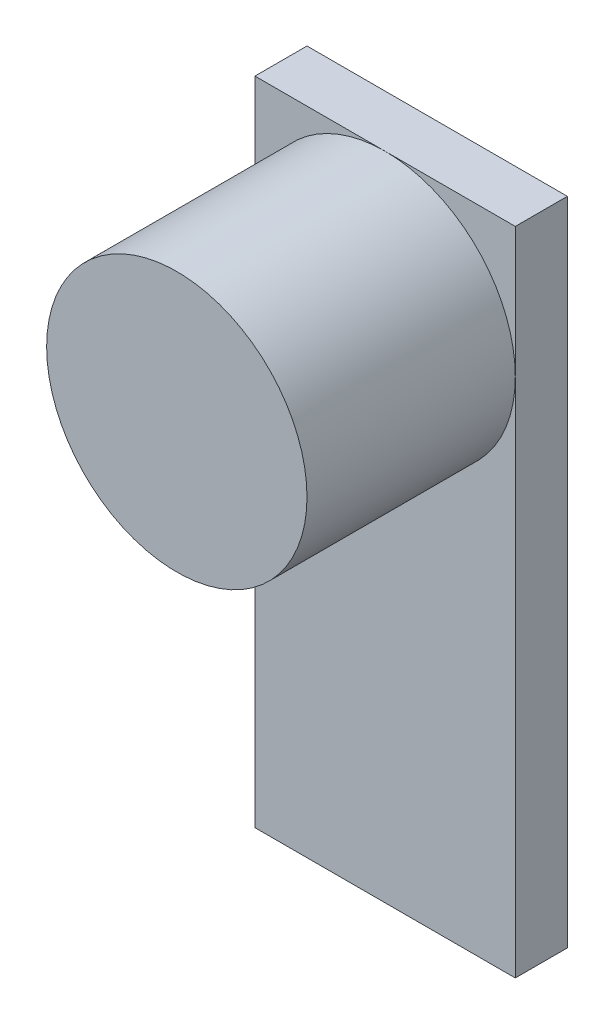
SolidWorks part; units mm, degrees
ref_plane "Front Plane" through (0, 0, 0) normal (0, 0, 1) x (1, 0, 0)
ref_plane "Top Plane" through (0, 0, 0) normal (0, 1, 0) x (1, 0, 0)
ref_plane "Right Plane" through (0, 0, 0) normal (1, 0, 0) x (0, 0, -1)
sketch "Sketch1" plane through (0, 0, 0) normal (0, 0, 1) x (1, 0, 0)
  line L5 (5000, 5000) -> (-5000, 5000)
  line L6 (5000, 5000) -> (5000, -20000)
  line L7 (5000, -20000) -> (-5000, -20000)
  line L8 (-5000, 5000) -> (-5000, -20000)
  circle A1 centre (0, 0) radius 5000
extrude "Boss-Extrude4" add sketch "Sketch1" along normal blind 10000 contours A1
extrude "Boss-Extrude5" add sketch "Sketch1<5>" along normal blind 2000 contours L6 L7 L8 L5
sketch "Sketch1<5>" plane through (0, 0, 0) normal (0, 0, 1) x (1, 0, 0) same geometry as "Sketch1"
